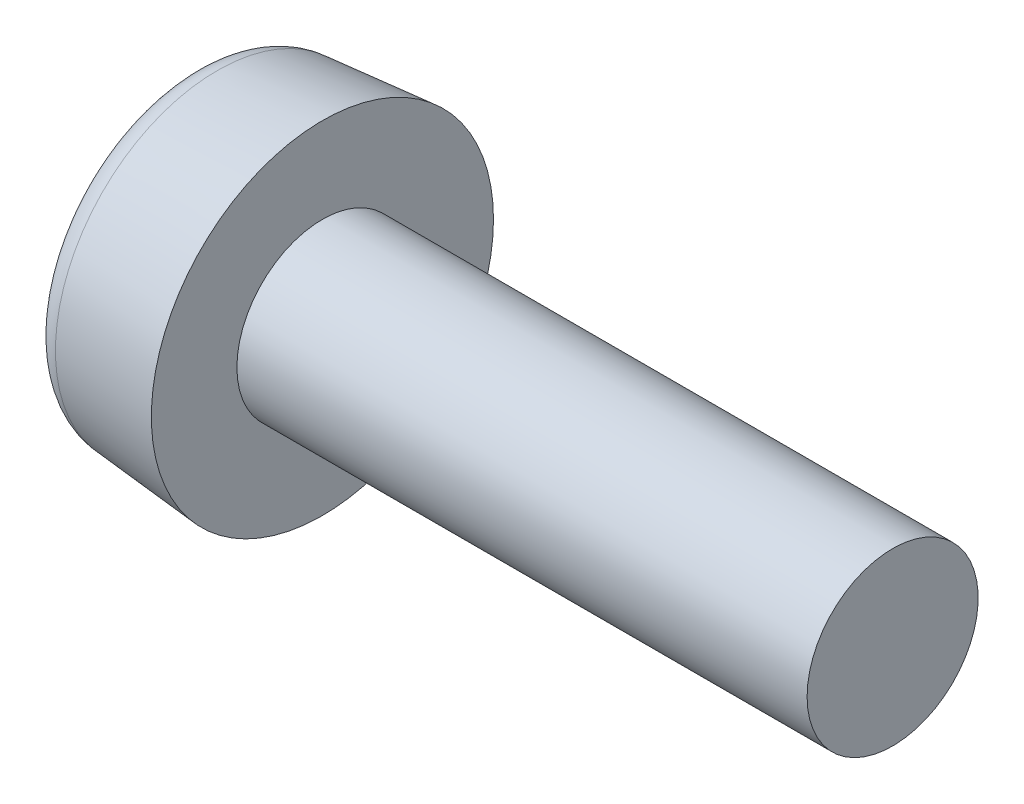
SolidWorks part; units mm, degrees
ref_plane "Front" through (0, 0, 0) normal (0, 0, 1) x (1, 0, 0)
ref_plane "Top" through (0, 0, 0) normal (0, 1, 0) x (1, 0, 0)
ref_plane "Right" through (0, 0, 0) normal (1, 0, 0) x (0, 0, -1)
ref_plane "Plane1" through (4.6, 0, 0) normal (1, 0, 0) x (0, 0, -1)
sketch "Sketch1" plane through (4.6, 0, 0) normal (1, 0, 0) x (0, 0, -1)
  circle A0 centre (0, 0) radius 6
  dimension "dk" = 12
extrude "BaseHead" add sketch "Sketch1" against normal blind 4.6 draft 5
sketch "Sketch2" plane through (4.6, 0, 0) normal (1, 0, 0) x (0, 0, -1)
  circle A0 centre (0, 0) radius 3
  dimension "d" = 6
sketch "Sketch8" plane through (0, 0, 0) normal (0, 0, 1) x (1, 0, 0)
  line L0 (0, 0) -> (35.73, 0) construction
  line L1 (6.964, 0) -> (6.964, -2) construction
  line L2 (4.6, -6) -> (4.6, 6) construction
  line L3 (11.6578, 0) -> (11.6578, -2) construction
  line L4 (4.6, 3) -> (24.6, 3)
  line L5 (24.6, 3) -> (24.6, 0)
  line L7 (24.6, 0) -> (4.6, 0)
  line L9 (4.6, 3) -> (4.6, 0)
  arc A0 (6.7996, -0.1884) -> (7.1407, -0.1768) centre (6.964, 0) ccw construction
  dimension "a" = 2
  dimension "l" = 20
  dimension "D4" = 2
  dimension "d" = 6
revolve "Revolve1" add sketch "Sketch8" angle 360 about L0
cosmetic thread "ThreadCosmetic1" [suppressed] parameters "bb"=18, "THD_MINOR"=4.5
sketch "Sketch4" plane through (0, 0, 0) normal (1, 0, 0) x (0, 0, -1)
  line L1 (0, 2.3094) -> (-2, 1.1547) construction
  line L2 (-2, 1.1547) -> (-2, -1.1547) construction
  line L3 (-2, -1.1547) -> (0, -2.3094) construction
  line L4 (0, -2.3094) -> (2, -1.1547) construction
  line L5 (2, -1.1547) -> (2, 1.1547) construction
  line L6 (2, 1.1547) -> (0, 2.3094) construction
  line L7 (1, 1.7321) -> (-1, 1.7321) construction
  line L8 (-1, 1.7321) -> (-2, 0) construction
  line L9 (-2, 0) -> (-1, -1.7321) construction
  line L10 (-1, -1.7321) -> (1, -1.7321) construction
  line L11 (1, -1.7321) -> (2, 0) construction
  line L12 (2, 0) -> (1, 1.7321) construction
  circle A0 centre (0, 0) radius 2.3094 construction
  circle A1 centre (0, 0) radius 2 construction
  spline S0 degree 3 poles (0, 2.6647) (0.9231, 1.5988) (2.3077, 1.3323) (1.8462, 0) (2.3077, -1.3323) (0.9231, -1.5988) (0, -2.6647) (-0.9231, -1.5988) (-2.3077, -1.3323) (-1.8462, 0) (-2.3077, 1.3323) (-0.9231, 1.5988) (0, 2.6647) (0.9231, 1.5988) (2.3077, 1.3323) knots -0.25 -0.166667 -0.083333 0 0.083333 0.166667 0.25 0.333333 0.416667 0.5 0.583333 0.666667 0.75 0.833333 0.916667 1 1.083333 1.166667 1.25 only from (1, 1.7321) to (1, 1.7321)
  dimension "B" = 4
extrude "Socket" cut sketch "Sketch4" along normal blind 2
sketch "Sketch5" plane through (2, 0, 0) normal (-1, 0, 0) x (0, 0, 1)
  spline S1 degree 3 poles (0, 2.6647) (-0.9231, 1.5988) (-2.3077, 1.3323) (-1.8462, 0) (-2.3077, -1.3323) (-0.9231, -1.5988) (0, -2.6647) (0.9231, -1.5988) (2.3077, -1.3323) (1.8462, 0) (2.3077, 1.3323) (0.9231, 1.5988) (0, 2.6647) (-0.9231, 1.5988) (-2.3077, 1.3323) knots -0.25 -0.166667 -0.083333 0 0.083333 0.166667 0.25 0.333333 0.416667 0.5 0.583333 0.666667 0.75 0.833333 0.916667 1 1.083333 1.166667 1.25 only from (-1, 1.7321) to (-1, 1.7321)
  spline S2 degree 3 poles (0, 2.6647) (-0.9231, 1.5988) (-2.3077, 1.3323) (-1.8462, 0) (-2.3077, -1.3323) (-0.9231, -1.5988) (0, -2.6647) (0.9231, -1.5988) (2.3077, -1.3323) (1.8462, 0) (2.3077, 1.3323) (0.9231, 1.5988) (0, 2.6647) (-0.9231, 1.5988) (-2.3077, 1.3323) knots -0.25 -0.166667 -0.083333 0 0.083333 0.166667 0.25 0.333333 0.416667 0.5 0.583333 0.666667 0.75 0.833333 0.916667 1 1.083333 1.166667 1.25 only from (-1, 1.7321) to (-1, 1.7321)
  dimension "D1" = 0
ref_plane "Plane2" through (2.6667, 0, 0) normal (-1, 0, 0) x (0, 0, 1)
sketch "Sketch7" plane through (2.6667, 0, 0) normal (-1, 0, 0) x (0, 0, 1)
  point P0 (0, 0)
loft "Cut-Loft1" cut profiles "Sketch7", "Sketch5"
sketch "Sketch6" plane through (-30.7487, 13.2487, 0) normal (0, 0, 1) x (0, -1, 0)
  line L0 (13.2487, 89.8637) -> (13.2487, 24.8312) construction
  line L1 (-4.0013, 35.3487) -> (10.8987, 35.3487)
  line L2 (-4.0013, 35.3487) -> (-4.0013, 45.3487)
  line L3 (-4.0013, 45.3487) -> (10.2487, 45.3487)
  line L4 (10.9987, 35.4487) -> (10.9987, 43.3487)
  line L5 (16.2487, 55.3487) -> (10.2487, 55.3487) construction
  line L6 (10.2487, 45.3487) -> (10.9987, 43.3487)
  line L9 (19.2487, 35.3487) -> (7.2487, 35.3487) construction
  arc A0 (10.8987, 35.3487) -> (10.9987, 35.4487) centre (10.8987, 35.4487) ccw
  dimension "r" = 0.1
  dimension "D2" = 15
  dimension "b" = 10
  dimension "D3" = 6
fillet "HeadFillet2" radius 1 1 edges at (0, 0, -5.5976)
sketch "Sketch9" plane through (0, 0, 0) normal (0, 0, 1) x (1, 0, 0)
  line L0 (24.6, 2.3505) -> (24.975, 3)
  line L1 (24.975, 3) -> (24.975, 3.75)
  line L2 (24.975, 3.75) -> (24.225, 3.75)
  line L3 (24.225, 3.75) -> (24.225, 3)
  line L4 (24.225, 3) -> (24.6, 2.3505)
  line L5 (24.6, -3) -> (24.6, 3) construction
  line L6 (0, 0) -> (28.2938, 0) construction
  line L7 (0, 4.6812) -> (0, -4.6812) construction
  dimension "D1" = 0.75
  dimension "D2" = 6
revolve "Cut-Revolve10" [suppressed] cut sketch "Sketch9" angle 360 about L6
pattern_linear "LPattern10" [suppressed] count 20 spacing 0.9 along (-1, 0, 0) of bodies 110
equation "\"D1@Plane1\"=\"k@BaseHead\""
equation "\"D1@Plane2\" = \"t@Socket\" / 3"
equation "\"D2@Sketch9\" =\"d@Sketch8\""
equation "\"D1@Sketch9\" =  ( \"d@Sketch8\" - \"THD_MINOR@ThreadCosmetic1\" )  / 2"
equation "\"D3@LPattern10\" = \"D1@Sketch9\" * 1.2"
equation "\"D1@LPattern10\" = \"bb@ThreadCosmetic1\" / \"D3@LPattern10\" "
equation "\"D3@Sketch6\" = \"d@Sketch8\""
